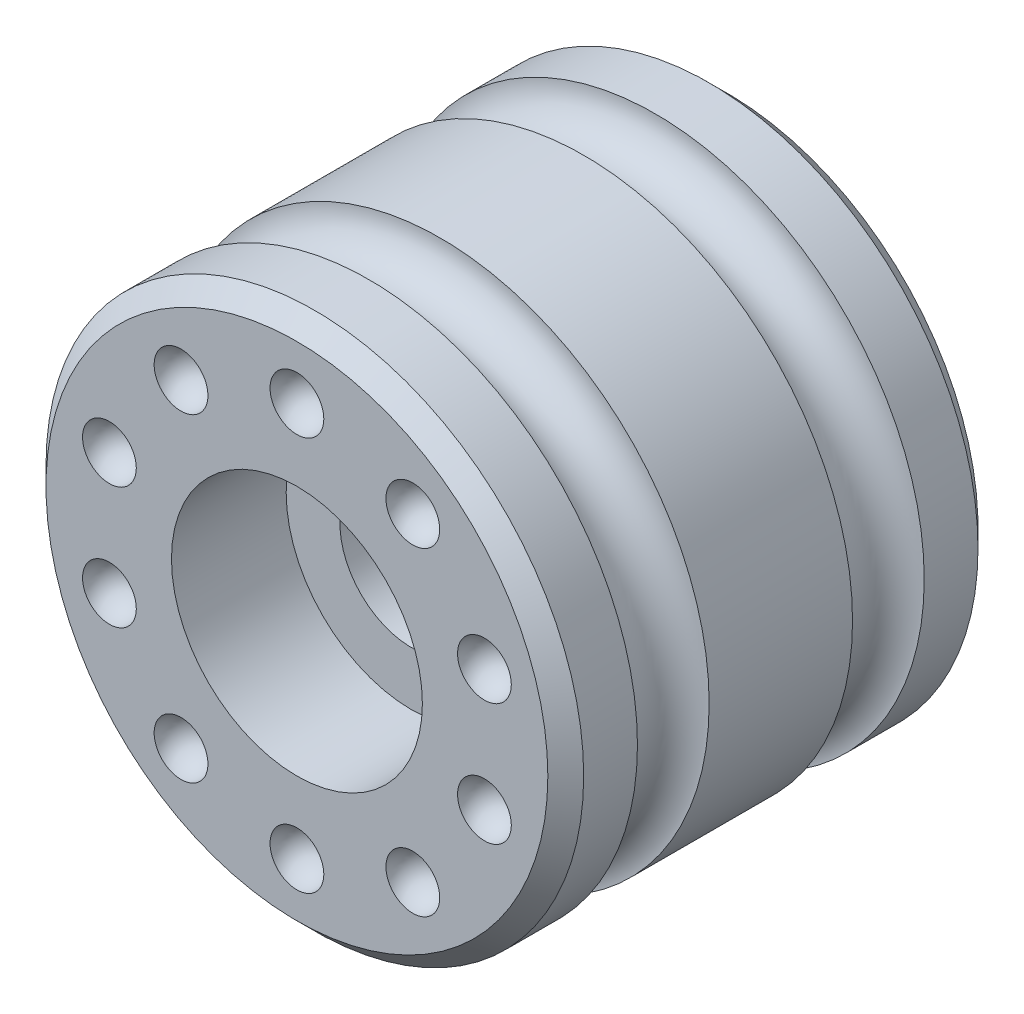
SolidWorks part; units mm, degrees
ref_plane "Front Plane" through (0, 0, 0) normal (0, 0, 1) x (1, 0, 0)
ref_plane "Top Plane" through (0, 0, 0) normal (0, 1, 0) x (1, 0, 0)
ref_plane "Right Plane" through (0, 0, 0) normal (1, 0, 0) x (0, 0, -1)
sketch "Sketch1" plane through (0, 0, 0) normal (0, 0, 1) x (1, 0, 0)
  circle A0 centre (0, 0) radius 7.5
  point P3 (0, 0)
  dimension "D1" = 15
extrude "Boss-Extrude1" add sketch "Sketch1" along normal blind 6
sketch "Sketch3" plane through (0, 0, 0) normal (1, 0, 0) x (0, 0, -1)
  line L0 (0, 7.5) -> (-6, 7.5) construction
  line L2 (0, -7.5) -> (0, 7.5) construction
  circle A0 centre (-3, 7.5) radius 1
  point P4 (0, 0)
  dimension "D1" = 2
  dimension "D2" = 3
ref_axis "Axis1" through (0, 0, -0.35) along (0, 0, 1)
revolve "Cut-Revolve1" cut sketch "Sketch3" angle 360 about axis through (0, 0, -0.35) along (0, 0, 1)
sketch "Sketch2" plane through (0, 0, 6) normal (0, 0, 1) x (1, 0, 0)
  circle A0 centre (0, 0) radius 3.5
  dimension "D1" = 7
extrude "Cut-Extrude1" cut sketch "Sketch2" against normal blind 3.2
chamfer "Chamfer1" distance 0.5 angle 45 1 edges at (7.5, 0, 6)
sketch "Sketch4" plane through (0, 0, 2.8) normal (0, 0, 1) x (1, 0, 0)
  circle A0 centre (0, 0) radius 2
  dimension "D1" = 4
extrude "Cut-Extrude2" cut sketch "Sketch4" against normal through all
ref_axis "Axis2" through (0, 55, 6) along (0, -1, 0)
sketch "Sketch6" plane through (0, 0, 0) normal (1, 0, 0) x (0, 0, -1)
  line L0 (-6, 55) -> (-6, -55) construction
  line L1 (-6, 4.75) -> (-6, 6.25)
  arc A0 (-6, 6.25) -> (-6, 4.75) centre (-6, 5.5) ccw
  dimension "D1" = 1.5
  dimension "D2" = 2
revolve "Cut-Revolve2" cut sketch "Sketch6" angle 360 about axis through (0, 55, 6) along (0, -1, 0)
pattern_circular "CirPattern1" count 10 over 360 about axis through (0, 0, -0.35) along (0, 0, 1) of "Cut-Revolve2" reverse direction yes
mirror "Mirror2" about plane through (0, 0, 0) normal (0, 0, 1) of "CirPattern1", "Cut-Revolve2", "Cut-Extrude2", "Chamfer1", "Cut-Extrude1", "Cut-Revolve1", "Boss-Extrude1"
